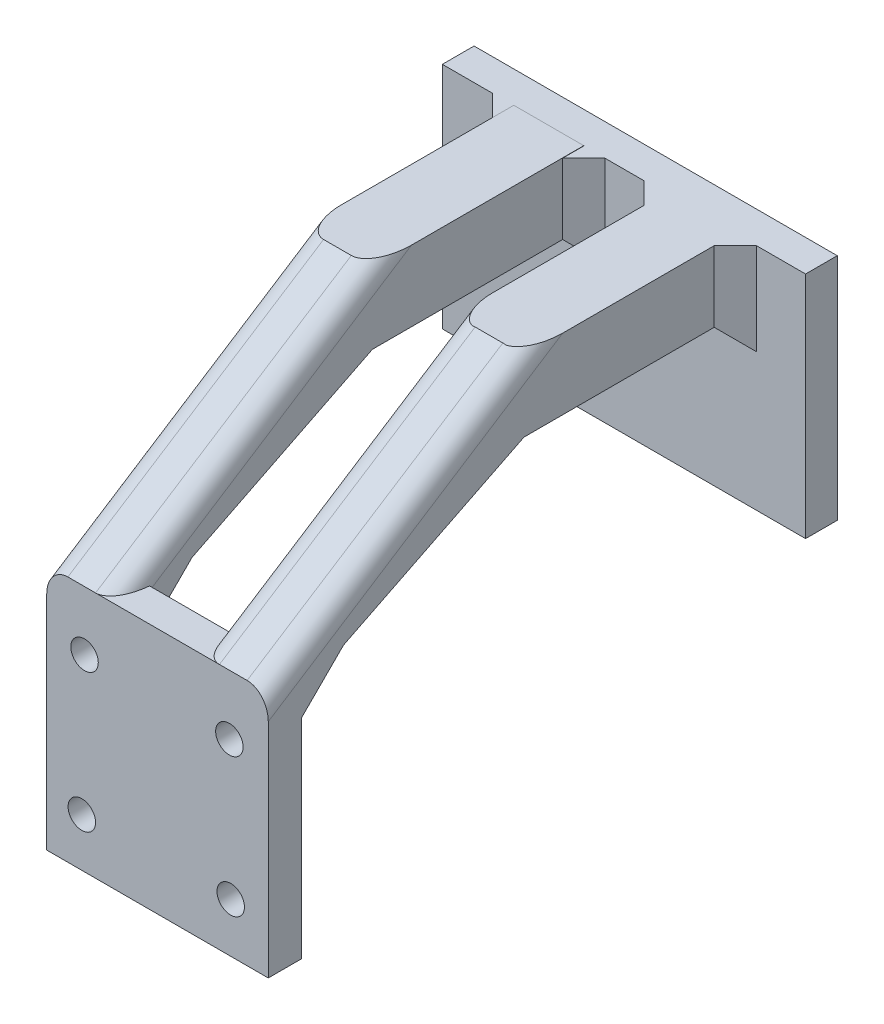
SolidWorks part; units mm, degrees
ref_plane "Front Plane" through (0, 0, 0) normal (0, 0, 1) x (1, 0, 0)
ref_plane "Top Plane" through (0, 0, 0) normal (0, 1, 0) x (1, 0, 0)
ref_plane "Right Plane" through (0, 0, 0) normal (1, 0, 0) x (0, 0, -1)
sketch "Sketch1" plane through (0, 0, 0) normal (0, 0, 1) x (1, 0, 0)
  line L0 (-9.5457, 9.836) -> (-9.5457, 31.5234)
  line L1 (-9.5457, 31.5234) -> (-43.914, 31.5234)
  line L2 (-43.914, 31.5234) -> (-43.9144, 9.836)
  line L3 (-43.9144, 9.836) -> (-9.5457, 9.836)
extrude "Boss-Extrude1" add sketch "Sketch1" along normal blind 3
sketch "Sketch2" plane through (0, 0, 3) normal (0, 0, 1) x (1, 0, 0)
  line L0 (-16.1902, 31.5234) -> (-16.1902, 24.832)
  line L1 (-9.5457, 31.5234) -> (-43.914, 31.5234) construction
  line L2 (-16.1902, 24.832) -> (-22.8107, 24.832)
  line L3 (-22.8107, 24.832) -> (-22.8107, 31.5234)
  line L4 (-22.8107, 31.5234) -> (-16.1902, 31.5234)
  line L5 (-37.1544, 24.8554) -> (-37.1544, 31.5468)
  line L6 (-37.1544, 31.5468) -> (-30.5338, 31.5468)
  line L7 (-30.5338, 31.5468) -> (-30.5338, 24.8554)
  line L8 (-30.5338, 24.8554) -> (-37.1544, 24.8554)
  point P11 (0, 0)
extrude "Boss-Extrude2" add sketch "Sketch2" along normal blind 20
sketch "Sketch3" plane through (-37.1544, 0, 0) normal (-1, 0, 0) x (0, 0, 1)
  line L0 (23, 31.5468) -> (47.197, 15.991)
  line L1 (47.197, 15.991) -> (47.197, 4.6067)
  line L2 (47.197, 4.6067) -> (44.067, 4.6067)
  line L3 (44.067, 4.6067) -> (44.067, 14.3414)
  line L4 (44.067, 14.3414) -> (23, 24.8554)
  line L5 (23, 31.5468) -> (23, 24.8554)
  point P6 (47.197, 15.991)
  point P9 (44.067, 14.3414)
sketch "Sketch4" plane through (-16.1902, 0, 0) normal (1, 0, 0) x (0, 0, -1)
  line L0 (-23, 31.5468) -> (-47.197, 15.991)
  line L1 (-47.197, 15.991) -> (-47.197, 4.6067)
  line L2 (-47.197, 4.6067) -> (-44.067, 4.6067)
  line L3 (-44.067, 4.6067) -> (-44.067, 14.3414)
  line L4 (-44.067, 14.3414) -> (-23, 24.832)
  line L5 (-23, 24.832) -> (-23, 31.5468)
extrude "Boss-Extrude3" add sketch "Sketch3" against normal up to vertex (6.6205 mm away) up to point (-30.5338, 24.8554, 23)
extrude "Boss-Extrude4" add sketch "Sketch4" against normal up to vertex (6.6205 mm away) up to point (-22.8107, 31.5234, 23)
sketch "Sketch5" plane through (0, 0, 47.197) normal (0, 0, 1) x (1, 0, 0)
  line L0 (-22.8107, 15.991) -> (-30.5338, 15.991)
  line L1 (-30.5338, 15.991) -> (-30.5338, 4.6067)
  line L2 (-30.5338, 4.6067) -> (-22.8107, 4.6067)
  line L3 (-22.8107, 4.6067) -> (-22.8107, 15.991)
extrude "Boss-Extrude5" add sketch "Sketch5" against normal up to vertex (3.1301 mm away) contours L3 L0 L1 L2 up to point (-30.5338, 14.3414, 44.067)
sketch "Sketch6" plane through (0, 4.6067, 0) normal (0, -1, 0) x (-1, 0, 0)
  line L0 (16.1902, -47.197) -> (16.1902, -44.067)
  line L1 (16.1902, -47.197) -> (16.1902, -44.067) construction
  line L2 (16.1902, -44.067) -> (37.1544, -44.067)
  line L3 (37.1544, -44.067) -> (37.1544, -47.197)
  line L4 (37.1544, -44.067) -> (37.1544, -47.197) construction
  line L5 (37.1544, -47.197) -> (16.1902, -47.197)
  point P5 (16.2247, -47.197)
extrude "Boss-Extrude6" add sketch "Sketch6" along normal blind 12
chamfer "Chamfer2" distance 2 angle 45 2 edges at (-33.8441, 24.8554, 3) (-37.1544, 28.1894, 3)
chamfer "Chamfer3" distance 2 angle 45 4 edges at (-16.1902, 28.1777, 3) (-19.5004, 24.832, 3) (-22.8107, 28.1777, 3) (-30.5338, 27.1894, 3)
fillet "Fillet1" radius 2 2 edges at (-22.8107, 23.7689, 35.0985) (-37.1544, 23.7689, 35.0985)
fillet "Fillet2" radius 2 2 edges at (-30.5338, 23.7689, 35.0985) (-16.1902, 23.7689, 35.0985)
chamfer "Chamfer10" distance 2 angle 45 1 edges at (-33.8441, 14.3414, 44.067) first distance on face at (-26.6723, 10.5814, 44.067)
chamfer "Chamfer11" distance 2 angle 45 1 edges at (-19.5004, 14.3414, 44.067) first distance on face at (-26.6723, 10.1814, 44.067)
sketch "Sketch8" plane through (0, 0, 47.197) normal (0, 0, 1) x (1, 0, 0)
  circle A0 centre (-19.8713, 10.3358) radius 1.3
  circle A1 centre (-19.7443, -2.7178) radius 1.3
  circle A2 centre (-33.8349, -2.8204) radius 1.3
  circle A3 centre (-33.5771, 10.403) radius 1.3
extrude "Cut-Extrude1" cut sketch "Sketch8" against normal blind 12
